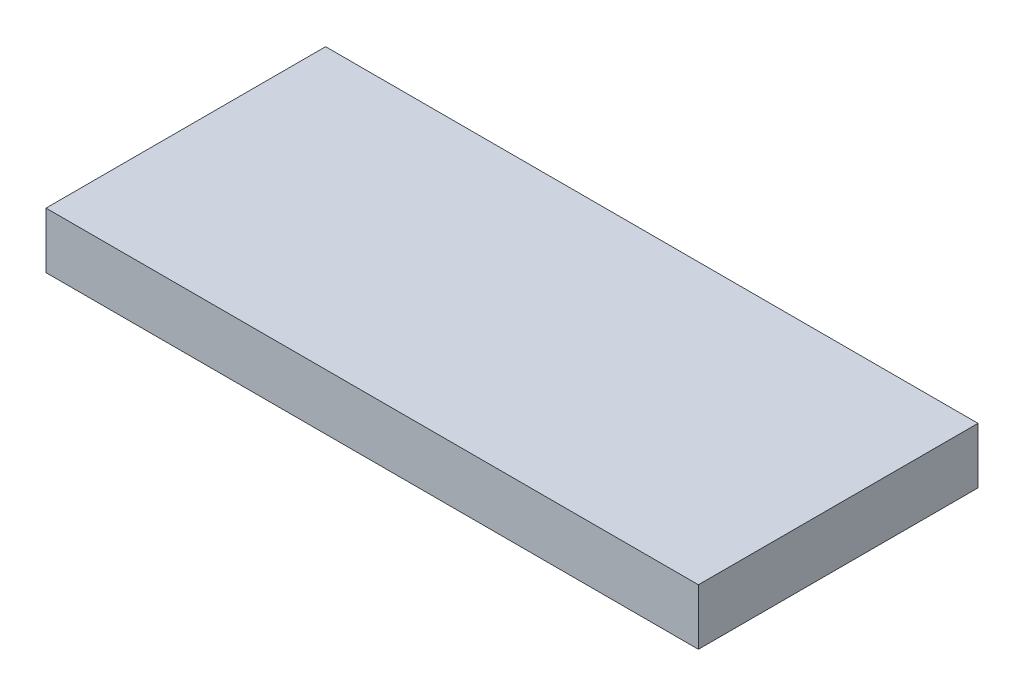
SolidWorks part; units mm, degrees
ref_plane "Front Plane" through (0, 0, 0) normal (0, 0, 1) x (1, 0, 0)
ref_plane "Top Plane" through (0, 0, 0) normal (0, 1, 0) x (1, 0, 0)
ref_plane "Right Plane" through (0, 0, 0) normal (1, 0, 0) x (0, 0, -1)
sketch "Sketch1" plane through (0, 0, 0) normal (0, 1, 0) x (1, 0, 0)
  line L1 (0, 0) -> (35, 0)
  line L2 (0, 0) -> (0, 15)
  line L3 (0, 15) -> (35, 15)
  line L4 (35, 0) -> (35, 15)
  dimension "D1" = 15
  dimension "D2" = 35
extrude "Boss-Extrude1" add sketch "Sketch1" along normal blind 3
